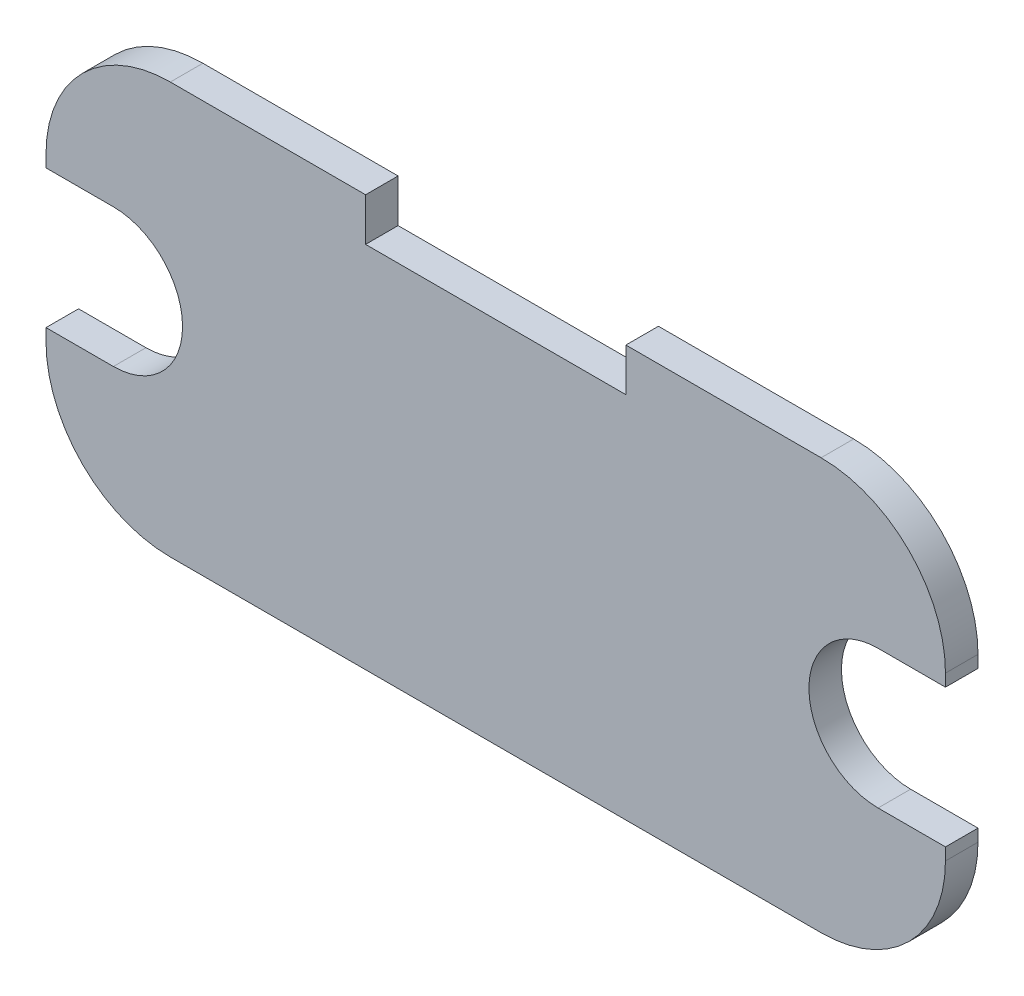
SolidWorks part; units mm, degrees
ref_plane "Спереди" through (0, 0, 0) normal (0, 0, 1) x (1, 0, 0)
ref_plane "Сверху" through (0, 0, 0) normal (0, 1, 0) x (1, 0, 0)
ref_plane "Справа" through (0, 0, 0) normal (1, 0, 0) x (0, 0, -1)
sketch "Эскиз1" plane through (0, 0, 0) normal (0, 0, 1) x (1, 0, 0)
  line L0 (-28.5, 3) -> (28.5, 3) construction
  line L1 (-20, 16.5) -> (-20, -10.5) construction
  line L2 (0, 16.5) -> (0, -10.5) construction
  line L3 (-20, 15.6424) -> (20, 15.6424)
  line L4 (-20, -9.6424) -> (20, -9.6424)
  line L5 (-27.6424, 8) -> (-27.6424, -2)
  line L6 (27.6424, 8) -> (27.6424, -2)
  line L7 (-8, 15.6424) -> (-8, 13)
  line L8 (28.5, 8) -> (28.5, -2)
  line L9 (-20, -10.5) -> (20, -10.5)
  line L10 (-28.5, 8) -> (-28.5, -2)
  line L11 (-8, 15) -> (-8, 13)
  line L12 (-8, 13) -> (8, 13)
  line L13 (8, 13) -> (8, 15)
  line L14 (8, 15) -> (-8, 15)
  line L15 (-20, 16.5) -> (20, 16.5)
  line L16 (8, 13) -> (8, 15.6424)
  circle A0 centre (-20, 8) radius 7.6424
  circle A1 centre (-20, -2) radius 7.6424
  circle A2 centre (20, -2) radius 7.6424
  circle A3 centre (20, 8) radius 7.6424
  arc A6 (20, -10.5) -> (28.5, -2) centre (20, -2) ccw
  arc A7 (-28.5, -2) -> (-20, -10.5) centre (-20, -2) ccw
  circle A8 centre (-23.5, 3) radius 3.25
  arc A10 (28.5, 8) -> (20, 16.5) centre (20, 8) ccw
  arc A11 (-20, 16.5) -> (-28.5, 8) centre (-20, 8) ccw
  circle A15 centre (23.5, 3) radius 3.25
extrude "Бобышка-Вытянуть1" add sketch "Эскиз1" along normal blind 2 contours A2 A3 L3 L16 L13 L12 L7 A0 A1 L4 | A8 A1 A0 | A8 A0 A1 | A8 A1 A0 | A8 A0 L5 A1 | A15 A3 A2 | A15 A3 A2 | A15 A2 A3 | A15 A2 L6 A3 region at (0, 2.2574, 0) region at (-19.7632, 9.7417, 0) region at (-27.2544, 3, 0) region at (-19.7632, -3.7417, 0) region at (-18.1292, 3, 0) region at (19.7632, 9.7417, 0) region at (27.2544, 3, 0) region at (19.7632, -3.7417, 0) region at (18.1292, 3, 0)
sketch "Эскиз3" plane through (0, 0, 2) normal (0, 0, 1) x (1, 0, 0)
  line L0 (-23.5, 3) -> (-30.3035, 3) construction
  line L1 (-23.5, -1.25) -> (-30.3035, -1.25)
  line L2 (-23.5, 7.25) -> (-30.3035, 7.25)
  line L3 (0, 13) -> (0, -9.6424) construction
  line L4 (-8, 13) -> (8, 13) construction
  line L5 (-20, -9.6424) -> (20, -9.6424) construction
  line L6 (23.5, 3) -> (30.3035, 3) construction
  line L7 (23.5, -1.25) -> (30.3035, -1.25)
  line L8 (23.5, 7.25) -> (30.3035, 7.25)
  arc A0 (-23.5, -1.25) -> (-23.5, 7.25) centre (-23.5, 3) ccw
  arc A1 (-30.3035, 7.25) -> (-30.3035, -1.25) centre (-30.3035, 3) ccw
  circle A2 centre (-23.5, 3) radius 3.25 construction
  arc A3 (23.5, -1.25) -> (23.5, 7.25) centre (23.5, 3) cw
  arc A4 (30.3035, 7.25) -> (30.3035, -1.25) centre (30.3035, 3) cw
  point P3 (-26.9017, 3)
  point P18 (26.9017, 3)
  dimension "D1" = 1
extrude "Вырез-Вытянуть2" cut sketch "Эскиз3" against normal blind 2
